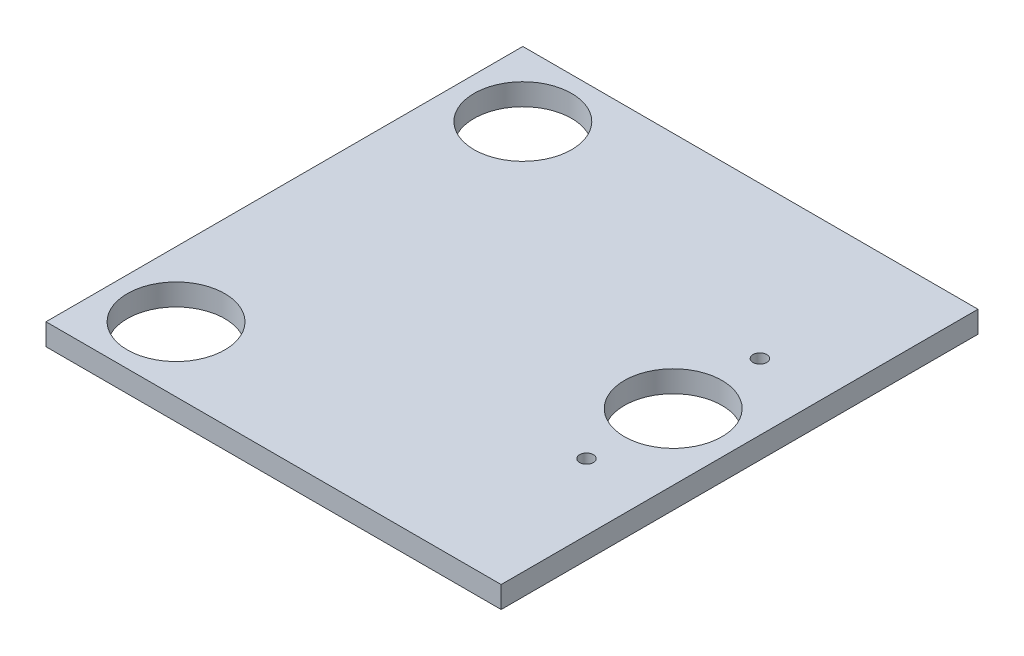
SolidWorks part; units mm, degrees
material "Cast Alloy Steel"
ref_plane "Front Plane" through (0, 0, 0) normal (0, 0, 1) x (1, 0, 0)
ref_plane "Top Plane" through (0, 0, 0) normal (0, 1, 0) x (1, 0, 0)
ref_plane "Right Plane" through (0, 0, 0) normal (1, 0, 0) x (0, 0, -1)
sketch "Sketch1" plane through (0, 0, 0) normal (0, 1, 0) x (1, 0, 0)
  line L0 (19.05, 50.8) -> (19.05, -50.8) construction
  line L1 (0, -69.85) -> (133.35, -69.85)
  line L2 (0, -69.85) -> (0, 69.85)
  line L3 (0, 69.85) -> (133.35, 69.85)
  line L4 (133.35, -69.85) -> (133.35, 69.85)
  line L5 (0, 69.85) -> (19.05, 50.8) construction
  line L6 (0, -69.85) -> (19.05, -50.8) construction
  line L7 (19.05, -50.8) -> (113.9007, 0) construction
  line L8 (113.9007, 0) -> (19.05, 50.8) construction
  circle A0 centre (19.05, 50.8) radius 14.2875
  circle A1 centre (19.05, -50.8) radius 14.2875
  circle A2 centre (113.9007, 0) radius 14.2875
  circle A3 centre (113.9007, 25.4) radius 2.0193
  circle A4 centre (113.9007, -25.4) radius 2.0193
  point P0 (0, 0)
  point P13 (0, 0)
  dimension "D2" = 19.05
  dimension "D3" = 28.575
  dimension "D4" = 101.6
  dimension "D1" = 107.5979
  dimension "D6" = 45
  dimension "D7" = 45
  dimension "D5" = 133.35
  dimension "D8" = 113.9007
  dimension "D9" = 107.5979
extrude "Boss-Extrude1" add sketch "Sketch1" along normal blind 6.35
